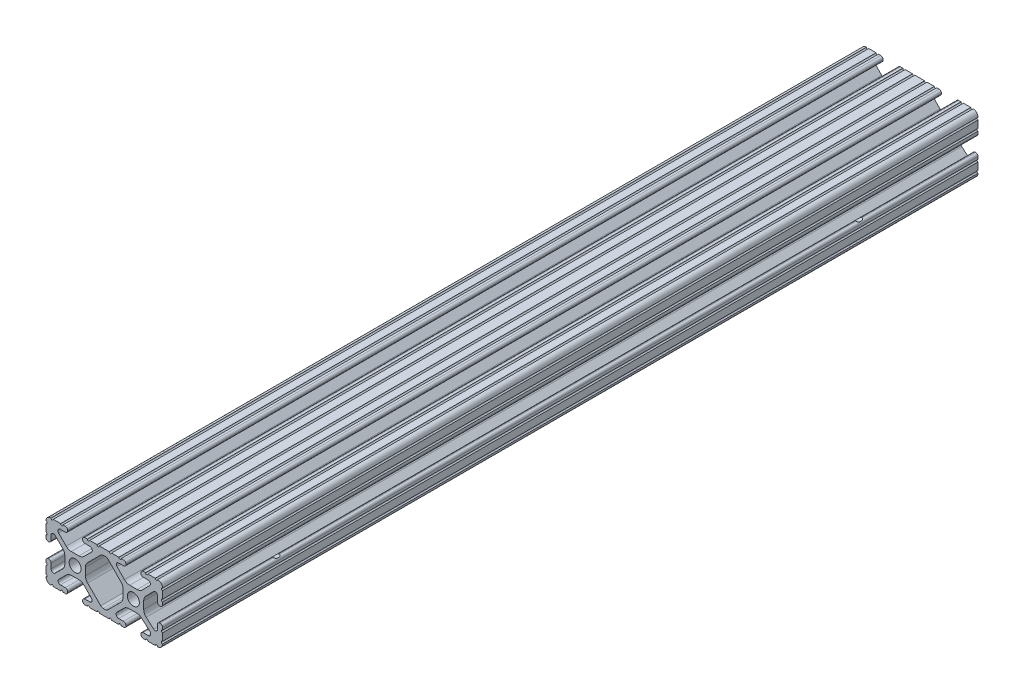
SolidWorks part; units mm, degrees
ref_plane "Front Plane" through (0, 0, 0) normal (0, 0, 1) x (1, 0, 0)
ref_plane "Top Plane" through (0, 0, 0) normal (0, 1, 0) x (1, 0, 0)
ref_plane "Right Plane" through (0, 0, 0) normal (1, 0, 0) x (0, 0, -1)
sketch "Sketch1" plane through (0, 0, 0) normal (0, 0, 1) x (1, 0, 0)
  line L0 (-7.2595, -3.8694) -> (-1.5457, -9.5728)
  line L1 (-8.1915, 1.6223) -> (-8.1915, -1.6223)
  line L2 (-1.504, 9.5765) -> (-7.252, 3.8768)
  line L3 (0.5515, 10.033) -> (-0.3952, 10.033)
  line L4 (7.2829, 3.8459) -> (1.6756, 9.5611)
  line L5 (8.1915, -1.6223) -> (8.1915, 1.6223)
  line L6 (1.5457, -9.5728) -> (7.2595, -3.8694)
  line L7 (-0.4332, -10.033) -> (0.4332, -10.033)
  line L8 (18.0171, 12.7) -> (16.9875, 12.7)
  line L9 (15.9385, 11.651) -> (15.9385, 11.5392)
  line L10 (16.9875, 10.4902) -> (19.1164, 10.4902)
  line L11 (19.8441, 8.7652) -> (16.619, 5.4551)
  line L12 (14.3449, 4.4958) -> (11.0833, 4.4958)
  line L13 (8.817, 5.4472) -> (5.5642, 8.7627)
  line L14 (6.2894, 10.4902) -> (8.4125, 10.4902)
  line L15 (9.4615, 11.5392) -> (9.4615, 11.651)
  line L16 (8.4125, 12.7) -> (7.3829, 12.7)
  line L17 (6.3669, 12.7) -> (3.1496, 12.7)
  line L18 (2.1336, 12.7) -> (-2.1336, 12.7)
  line L19 (-3.1496, 12.7) -> (-6.3669, 12.7)
  line L20 (-7.3829, 12.7) -> (-8.4125, 12.7)
  line L21 (-9.4615, 11.651) -> (-9.4615, 11.5392)
  line L22 (-8.4125, 10.4902) -> (-6.2836, 10.4902)
  line L23 (-5.5326, 8.6661) -> (-8.81, 5.4163)
  line L24 (-11.0455, 4.4958) -> (-14.3545, 4.4958)
  line L25 (-16.59, 5.4163) -> (-19.8674, 8.6661)
  line L26 (-19.1164, 10.4902) -> (-16.9875, 10.4902)
  line L27 (-15.9385, 11.5392) -> (-15.9385, 11.651)
  line L28 (-16.9875, 12.7) -> (-18.0171, 12.7)
  line L29 (-19.0331, 12.7) -> (-22.2504, 12.7)
  line L30 (-25.4, 9.5504) -> (-25.4, 6.3331)
  line L31 (-25.4, 5.3171) -> (-25.4, 4.2375)
  line L32 (-24.401, 3.2385) -> (-24.2392, 3.2385)
  line L33 (-23.1902, 4.2875) -> (-23.1902, 6.3347)
  line L34 (-21.434, 7.0665) -> (-18.148, 3.8082)
  line L35 (-17.2085, 1.5536) -> (-17.2085, -1.6952)
  line L36 (-18.1405, -3.9423) -> (-21.4316, -7.2274)
  line L37 (-23.1902, -6.498) -> (-23.1902, -4.2875)
  line L38 (-24.2392, -3.2385) -> (-24.351, -3.2385)
  line L39 (-25.4, -4.2875) -> (-25.4, -5.3171)
  line L40 (-25.4, -6.3331) -> (-25.4, -9.5504)
  line L41 (-22.2504, -12.7) -> (-19.0331, -12.7)
  line L42 (-18.0171, -12.7) -> (-16.9875, -12.7)
  line L43 (-15.9384, -11.651) -> (-15.9384, -11.5392)
  line L44 (-16.9875, -10.4902) -> (-19.1164, -10.4902)
  line L45 (-19.8341, -8.7551) -> (-16.4966, -5.4237)
  line L46 (-14.2536, -4.4958) -> (-11.1464, -4.4958)
  line L47 (-8.9034, -5.4237) -> (-5.5659, -8.7551)
  line L48 (-6.2836, -10.4902) -> (-8.4125, -10.4902)
  line L49 (-9.4616, -11.5392) -> (-9.4616, -11.651)
  line L50 (-8.4125, -12.7) -> (-7.3829, -12.7)
  line L51 (-6.3669, -12.7) -> (-3.1496, -12.7)
  line L52 (-2.1336, -12.7) -> (2.1336, -12.7)
  line L53 (3.1496, -12.7) -> (6.3669, -12.7)
  line L54 (7.3829, -12.7) -> (8.4125, -12.7)
  line L55 (9.4616, -11.651) -> (9.4616, -11.5392)
  line L56 (8.4125, -10.4902) -> (6.2894, -10.4902)
  line L57 (5.4807, -8.5353) -> (8.5979, -5.4237)
  line L58 (10.8409, -4.4958) -> (14.1026, -4.4958)
  line L59 (16.1879, -5.2766) -> (19.8682, -8.4822)
  line L60 (19.1164, -10.4902) -> (16.9875, -10.4902)
  line L61 (15.9384, -11.5392) -> (15.9384, -11.651)
  line L62 (16.9875, -12.7) -> (18.0171, -12.7)
  line L63 (19.0331, -12.7) -> (22.2504, -12.7)
  line L64 (25.4, -9.5504) -> (25.4, -6.3331)
  line L65 (25.4, -5.3171) -> (25.4, -4.2375)
  line L66 (24.401, -3.2385) -> (24.1892, -3.2385)
  line L67 (23.1902, -4.2375) -> (23.1902, -6.1559)
  line L68 (21.584, -6.8869) -> (18.2982, -4.025)
  line L69 (17.2085, -1.6308) -> (17.2085, 1.6308)
  line L70 (18.1094, 3.8465) -> (21.5263, 7.3534)
  line L71 (23.1902, 6.6769) -> (23.1902, 4.2375)
  line L72 (24.1892, 3.2385) -> (24.401, 3.2385)
  line L73 (25.4, 4.2375) -> (25.4, 5.3171)
  line L74 (25.4, 6.3332) -> (25.4, 9.5504)
  line L75 (22.2504, 12.7) -> (19.0331, 12.7)
  circle A0 centre (-12.7, 0) radius 2.6035
  circle A1 centre (12.7, 0) radius 2.6035
  arc A2 (-1.5457, -9.5728) -> (-0.4332, -10.033) centre (-0.4332, -8.4582) ccw
  arc A3 (-8.1915, -1.6223) -> (-7.2595, -3.8694) centre (-5.0165, -1.6223) ccw
  arc A4 (-7.252, 3.8768) -> (-8.1915, 1.6223) centre (-5.0165, 1.6223) ccw
  arc A5 (-0.3952, 10.033) -> (-1.504, 9.5765) centre (-0.3952, 8.4582) ccw
  arc A6 (1.6756, 9.5611) -> (0.5515, 10.033) centre (0.5515, 8.4582) ccw
  arc A7 (8.1915, 1.6223) -> (7.2829, 3.8459) centre (5.0165, 1.6223) ccw
  arc A8 (7.2595, -3.8694) -> (8.1915, -1.6223) centre (5.0165, -1.6223) ccw
  arc A9 (0.4332, -10.033) -> (1.5457, -9.5728) centre (0.4332, -8.4582) ccw
  arc A10 (18.0171, 12.7) -> (19.0331, 12.7) centre (18.5251, 12.7) ccw
  arc A11 (16.9875, 12.7) -> (15.9385, 11.651) centre (16.9875, 11.651) ccw
  arc A12 (15.9385, 11.5392) -> (16.9875, 10.4902) centre (16.9875, 11.5392) ccw
  arc A13 (19.8441, 8.7652) -> (19.1164, 10.4902) centre (19.1164, 9.4742) ccw
  arc A14 (14.3449, 4.4958) -> (16.619, 5.4551) centre (14.3449, 7.6708) ccw
  arc A15 (8.817, 5.4472) -> (11.0833, 4.4958) centre (11.0833, 7.6708) ccw
  arc A16 (6.2894, 10.4902) -> (5.5642, 8.7627) centre (6.2894, 9.4742) ccw
  arc A17 (8.4125, 10.4902) -> (9.4615, 11.5392) centre (8.4125, 11.5392) ccw
  arc A18 (9.4615, 11.651) -> (8.4125, 12.7) centre (8.4125, 11.651) ccw
  arc A19 (6.3669, 12.7) -> (7.3829, 12.7) centre (6.8749, 12.7) ccw
  arc A20 (2.1336, 12.7) -> (3.1496, 12.7) centre (2.6416, 12.7) ccw
  arc A21 (-3.1496, 12.7) -> (-2.1336, 12.7) centre (-2.6416, 12.7) ccw
  arc A22 (-7.3829, 12.7) -> (-6.3669, 12.7) centre (-6.8749, 12.7) ccw
  arc A23 (-8.4125, 12.7) -> (-9.4615, 11.651) centre (-8.4125, 11.651) ccw
  arc A24 (-9.4615, 11.5392) -> (-8.4125, 10.4902) centre (-8.4125, 11.5392) ccw
  arc A25 (-5.5326, 8.6661) -> (-6.2836, 10.4902) centre (-6.2836, 9.4235) ccw
  arc A26 (-11.0455, 4.4958) -> (-8.81, 5.4163) centre (-11.0455, 7.6708) ccw
  arc A27 (-16.59, 5.4163) -> (-14.3545, 4.4958) centre (-14.3545, 7.6708) ccw
  arc A28 (-19.1164, 10.4902) -> (-19.8674, 8.6661) centre (-19.1164, 9.4235) ccw
  arc A29 (-16.9875, 10.4902) -> (-15.9385, 11.5392) centre (-16.9875, 11.5392) ccw
  arc A30 (-15.9385, 11.651) -> (-16.9875, 12.7) centre (-16.9875, 11.651) ccw
  arc A31 (-19.0331, 12.7) -> (-18.0171, 12.7) centre (-18.5251, 12.7) ccw
  arc A32 (-23.2664, 12.6998) -> (-22.2504, 12.7) centre (-22.7584, 12.7) ccw
  arc A33 (-23.2664, 12.6998) -> (-25.3998, 10.5664) centre (-23.2918, 10.5918) ccw
  arc A34 (-25.4, 9.5504) -> (-25.3998, 10.5664) centre (-25.4, 10.0584) ccw
  arc A35 (-25.4, 5.3171) -> (-25.4, 6.3331) centre (-25.4, 5.8251) ccw
  arc A36 (-25.4, 4.2375) -> (-24.401, 3.2385) centre (-24.401, 4.2375) ccw
  arc A37 (-24.2392, 3.2385) -> (-23.1902, 4.2875) centre (-24.2392, 4.2875) ccw
  arc A38 (-21.434, 7.0665) -> (-23.1902, 6.3347) centre (-22.1596, 6.3347) ccw
  arc A39 (-17.2085, 1.5536) -> (-18.148, 3.8082) centre (-20.3835, 1.5536) ccw
  arc A40 (-18.1405, -3.9423) -> (-17.2085, -1.6952) centre (-20.3835, -1.6952) ccw
  arc A41 (-23.1902, -6.498) -> (-21.4316, -7.2274) centre (-22.1596, -6.498) ccw
  arc A42 (-23.1902, -4.2875) -> (-24.2392, -3.2385) centre (-24.2392, -4.2875) ccw
  arc A43 (-24.351, -3.2385) -> (-25.4, -4.2875) centre (-24.351, -4.2875) ccw
  arc A44 (-25.4, -6.3331) -> (-25.4, -5.3171) centre (-25.4, -5.8251) ccw
  arc A45 (-25.3998, -10.5664) -> (-25.4, -9.5504) centre (-25.4, -10.0584) ccw
  arc A46 (-25.3998, -10.5664) -> (-23.2664, -12.6998) centre (-23.2918, -10.5918) ccw
  arc A47 (-22.2504, -12.7) -> (-23.2664, -12.6998) centre (-22.7584, -12.7) ccw
  arc A48 (-18.0171, -12.7) -> (-19.0331, -12.7) centre (-18.5251, -12.7) ccw
  arc A49 (-16.9875, -12.7) -> (-15.9384, -11.651) centre (-16.9875, -11.651) ccw
  arc A50 (-15.9384, -11.5392) -> (-16.9875, -10.4902) centre (-16.9875, -11.5392) ccw
  arc A51 (-19.8341, -8.7551) -> (-19.1164, -10.4902) centre (-19.1164, -9.4742) ccw
  arc A52 (-14.2536, -4.4958) -> (-16.4966, -5.4237) centre (-14.2536, -7.6708) ccw
  arc A53 (-8.9034, -5.4237) -> (-11.1464, -4.4958) centre (-11.1464, -7.6708) ccw
  arc A54 (-6.2836, -10.4902) -> (-5.5659, -8.7551) centre (-6.2836, -9.4742) ccw
  arc A55 (-8.4125, -10.4902) -> (-9.4616, -11.5392) centre (-8.4125, -11.5392) ccw
  arc A56 (-9.4616, -11.651) -> (-8.4125, -12.7) centre (-8.4125, -11.651) ccw
  arc A57 (-6.3669, -12.7) -> (-7.3829, -12.7) centre (-6.8749, -12.7) ccw
  arc A58 (-2.1336, -12.7) -> (-3.1496, -12.7) centre (-2.6416, -12.7) ccw
  arc A59 (3.1496, -12.7) -> (2.1336, -12.7) centre (2.6416, -12.7) ccw
  arc A60 (7.3829, -12.7) -> (6.3669, -12.7) centre (6.8749, -12.7) ccw
  arc A61 (8.4125, -12.7) -> (9.4616, -11.651) centre (8.4125, -11.651) ccw
  arc A62 (9.4616, -11.5392) -> (8.4125, -10.4902) centre (8.4125, -11.5392) ccw
  arc A63 (5.4807, -8.5353) -> (6.2894, -10.4902) centre (6.2894, -9.3455) ccw
  arc A64 (10.8409, -4.4958) -> (8.5979, -5.4237) centre (10.8409, -7.6708) ccw
  arc A65 (16.1879, -5.2766) -> (14.1026, -4.4958) centre (14.1026, -7.6708) ccw
  arc A66 (19.1164, -10.4902) -> (19.8682, -8.4822) centre (19.1164, -9.3455) ccw
  arc A67 (16.9875, -10.4902) -> (15.9384, -11.5392) centre (16.9875, -11.5392) ccw
  arc A68 (15.9384, -11.651) -> (16.9875, -12.7) centre (16.9875, -11.651) ccw
  arc A69 (19.0331, -12.7) -> (18.0171, -12.7) centre (18.5251, -12.7) ccw
  arc A70 (23.2664, -12.6998) -> (22.2504, -12.7) centre (22.7584, -12.7) ccw
  arc A71 (23.2664, -12.6998) -> (25.3998, -10.5664) centre (23.2918, -10.5918) ccw
  arc A72 (25.4, -9.5504) -> (25.3998, -10.5664) centre (25.4, -10.0584) ccw
  arc A73 (25.4, -5.3171) -> (25.4, -6.3331) centre (25.4, -5.8251) ccw
  arc A74 (25.4, -4.2375) -> (24.401, -3.2385) centre (24.401, -4.2375) ccw
  arc A75 (24.1892, -3.2385) -> (23.1902, -4.2375) centre (24.1892, -4.2375) ccw
  arc A76 (21.584, -6.8869) -> (23.1902, -6.1559) centre (22.2207, -6.1559) ccw
  arc A77 (17.2085, -1.6308) -> (18.2982, -4.025) centre (20.3835, -1.6308) ccw
  arc A78 (18.1094, 3.8465) -> (17.2085, 1.6308) centre (20.3835, 1.6308) ccw
  arc A79 (23.1902, 6.6769) -> (21.5263, 7.3534) centre (22.2207, 6.6769) ccw
  arc A80 (23.1902, 4.2375) -> (24.1892, 3.2385) centre (24.1892, 4.2375) ccw
  arc A81 (24.401, 3.2385) -> (25.4, 4.2375) centre (24.401, 4.2375) ccw
  arc A82 (25.4, 6.3332) -> (25.4, 5.3171) centre (25.4, 5.8251) ccw
  arc A83 (25.3998, 10.5664) -> (25.4, 9.5504) centre (25.4, 10.0584) ccw
  arc A84 (25.3998, 10.5664) -> (23.2664, 12.6998) centre (23.2918, 10.5918) ccw
  arc A85 (22.2504, 12.7) -> (23.2664, 12.6998) centre (22.7584, 12.7) ccw
  point P248 (0, 10.033)
extrude "Boss-Extrude1" add sketch "Sketch1" along normal mid plane 355.6
sketch "Sketch2" plane through (25.4, 0, 0) normal (1, 0, 0) x (0, 0, -1)
  line L0 (0, 0) -> (-177.8, 0) construction
  line L1 (-177.8, -1.6308) -> (-177.8, 1.6308) construction
  circle A0 centre (-127, 0) radius 3.5
  dimension "D1" = 7
  dimension "D2" = 50.8
extrude "Cut-Extrude1" cut sketch "Sketch2" against normal through all
mirror "Mirror1" about plane through (0, 0, 0) normal (0, 0, 1) of "Cut-Extrude1"
